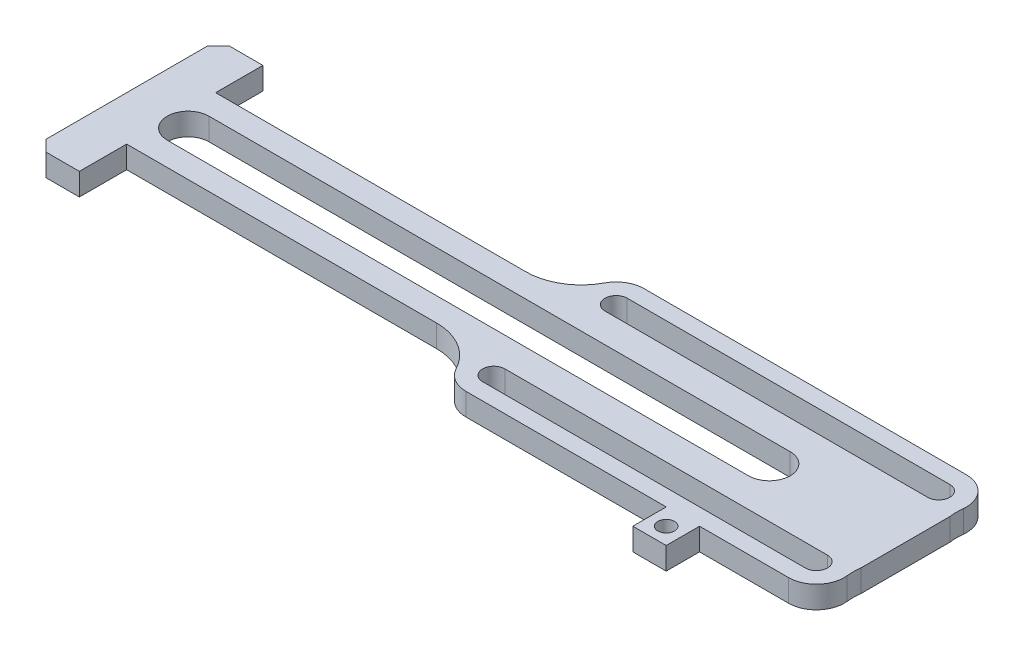
SolidWorks part; units mm, degrees
ref_plane "Спереди" through (0, 0, 0) normal (0, 0, 1) x (1, 0, 0)
ref_plane "Сверху" through (0, 0, 0) normal (0, 1, 0) x (1, 0, 0)
ref_plane "Справа" through (0, 0, 0) normal (1, 0, 0) x (0, 0, -1)
sketch "Эскиз1" plane through (0, 0, 0) normal (0, 1, 0) x (1, 0, 0)
  line L0 (0, 0) -> (-140, 0) construction
  line L1 (-140, -14.5) -> (-140, 14.5)
  line L2 (-140, 14.5) -> (-138, 16.5)
  line L3 (-138, 16.5) -> (-132, 16.5)
  line L4 (-132, 16.5) -> (-132, 8)
  line L5 (-132, 8) -> (0, 8)
  line L6 (0, 8) -> (0, -8)
  line L7 (-132, -8) -> (0, -8)
  line L8 (-132, -16.5) -> (-132, -8)
  line L9 (-138, -16.5) -> (-132, -16.5)
  line L10 (-140, -14.5) -> (-138, -16.5)
  dimension "D1" = 33
  dimension "D2" = 135
  dimension "D3" = 8
  dimension "D4" = 6
  dimension "D5" = 140
  dimension "D6" = 16
extrude "Бобышка-Вытянуть1" add sketch "Эскиз1" along normal blind 4
sketch "Эскиз2" plane through (0, 0, 0) normal (0, -1, 0) x (1, 0, 0)
  line L0 (0, 0) -> (-174.855, 0) construction
  line L1 (-63, 11) -> (-5, 11) construction
  line L2 (-63, 13) -> (-5, 13)
  line L3 (-63, 9) -> (-5, 9)
  line L4 (-63, 11) -> (-5, 11) construction
  line L5 (-63, 16) -> (-5, 16)
  line L6 (-63, 6) -> (-5, 6)
  line L8 (-63, -11) -> (-5, -11) construction
  line L9 (-63, -13) -> (-5, -13)
  line L10 (-63, -9) -> (-5, -9)
  line L11 (-63, -11) -> (-5, -11) construction
  line L12 (-63, -16) -> (-5, -16)
  line L13 (-63, -6) -> (-5, -6)
  arc A0 (-63, 13) -> (-63, 9) centre (-63, 11) ccw
  arc A1 (-5, 9) -> (-5, 13) centre (-5, 11) ccw
  arc A2 (-63, 16) -> (-63, 6) centre (-63, 11) ccw
  arc A3 (-5, 6) -> (-5, 16) centre (-5, 11) ccw
  arc A4 (-63, -13) -> (-63, -9) centre (-63, -11) cw
  arc A5 (-5, -9) -> (-5, -13) centre (-5, -11) cw
  arc A6 (-63, -16) -> (-63, -6) centre (-63, -11) cw
  arc A7 (-5, -6) -> (-5, -16) centre (-5, -11) cw
  point P5 (-34, 11)
  point P11 (-34, 11)
  point P21 (-34, -11)
  point P28 (-34, -11)
  dimension "D1" = 4
  dimension "D2" = 10
  dimension "D3" = 58
  dimension "D4" = 22
  dimension "D5" = 5
extrude "Бобышка-Вытянуть2" add sketch "Эскиз2" against normal up to surface (4 mm away) up to face at (-108.4, 4, 0)
fillet "Скругление1" radius 10 4 edges at (-1, 2, 8) (-1, 2, -8) (-67, 2, -8) (-67, 2, 8)
sketch "Эскиз3" plane through (0, 0, 0) normal (0, -1, 0) x (1, 0, 0)
  line L0 (-24.4476, 3.7538) -> (-128.9506, 3.7538)
  line L1 (-128.9506, -3.7462) -> (-24.4476, -3.7462)
  line L2 (-24.4476, 1.5038) -> (-128.9506, 1.5038)
  line L3 (-128.9506, -1.4962) -> (-24.4476, -1.4962)
  line L4 (-24.4476, 1.5038) -> (-128.9506, 1.5038) construction
  line L5 (-128.9506, -1.4962) -> (-24.4476, -1.4962) construction
  arc A0 (-128.9506, 3.7538) -> (-128.9506, -3.7462) centre (-128.9506, 0.0038) ccw
  arc A1 (-24.4476, -3.7462) -> (-24.4476, 3.7538) centre (-24.4476, 0.0038) ccw
  arc A2 (-128.9506, 1.5038) -> (-128.9506, -1.4962) centre (-128.9506, 0.0038) ccw
  arc A3 (-24.4476, -1.4962) -> (-24.4476, 1.5038) centre (-24.4476, 0.0038) ccw
  arc A4 (-128.9506, 1.5038) -> (-128.9506, -1.4962) centre (-128.9506, 0.0038) ccw construction
  arc A5 (-24.4476, -1.4962) -> (-24.4476, 1.5038) centre (-24.4476, 0.0038) ccw construction
  dimension "D3" = 7.5
  dimension "D1" = 0
  dimension "D2" = 2.25
extrude "Вырез-Вытянуть1" cut sketch "Эскиз3" against normal through all
sketch "Эскиз4" plane through (0, 4, 0) normal (0, 1, 0) x (1, 0, 0)
  line L1 (-21, -22) -> (-27, -22)
  line L2 (-21, -22) -> (-21, -16)
  line L3 (-21, -16) -> (-27, -16)
  line L4 (-27, -22) -> (-27, -16)
  line L5 (-21, -22) -> (-27, -16) construction
  line L6 (-21, -16) -> (-27, -22) construction
  line L7 (-63, -16) -> (-5, -16) construction
  line L8 (0, -8) -> (0, 8) construction
  point P0 (-24, -19)
  point P5 (-33.3598, 14.4632)
  point P6 (-33.3292, 14.5548)
  point P7 (0, 0)
  point P8 (-21.3757, 25.6114)
  point P9 (-29.9209, 16)
  point P10 (-24.6914, 21.1848)
  point P11 (-18.798, -21.998)
  point P12 (0, 0)
  point P13 (-22.3347, -16)
  point P16 (-19.337, -19)
  dimension "D1" = 6
  dimension "D2" = 6
  dimension "D3" = 21
extrude "Бобышка-Вытянуть7" add sketch "Эскиз4" against normal blind 4
sketch "Эскиз6" plane through (0, 4, 0) normal (0, 1, 0) x (1, 0, 0)
  line L0 (-27, -16) -> (-21, -22) construction
  circle A0 centre (-24, -19) radius 1.5
  point P6 (-19, -19)
  dimension "D1" = 3
extrude "Вырез-Вытянуть4" cut sketch "Эскиз6" against normal through all
